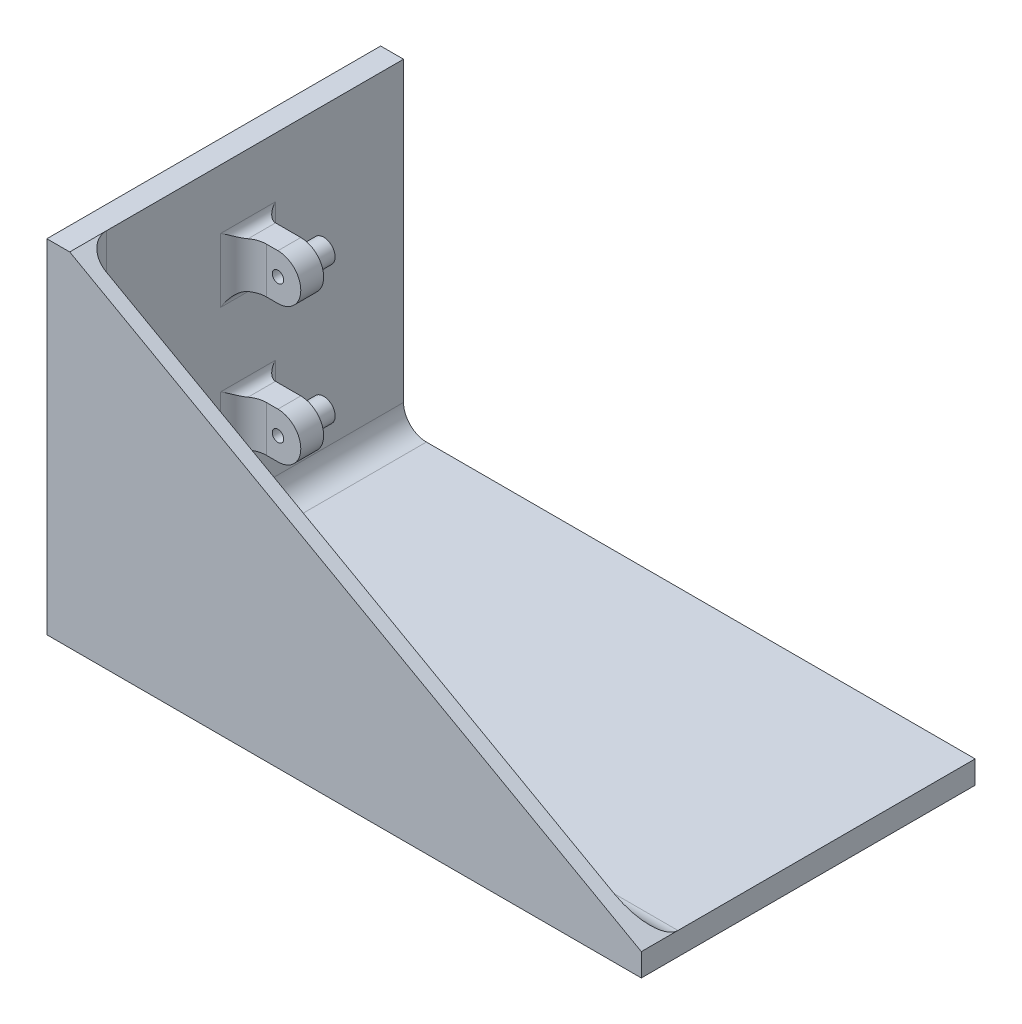
SolidWorks part; units mm, degrees
material "PET"
ref_plane "Piano frontale" through (0, 0, 0) normal (0, 0, 1) x (1, 0, 0)
ref_plane "Piano superiore" through (0, 0, 0) normal (0, 1, 0) x (1, 0, 0)
ref_plane "Piano destro" through (0, 0, 0) normal (1, 0, 0) x (0, 0, -1)
sketch "Schizzo1" plane through (0, 0, 0) normal (0, 0, 1) x (1, 0, 0)
  line L1 (0, 0) -> (-5, 0)
  line L2 (0, 0) -> (0, 70)
  line L3 (0, 70) -> (-5, 70)
  line L4 (-5, 0) -> (-5, 70)
  dimension "D1" = 70
  dimension "D2" = 5
extrude "Estrusione-Estrusione1" add sketch "Schizzo1" along normal blind 70
sketch "Schizzo2" plane through (0, 0, 70) normal (0, 0, 1) x (1, 0, 0)
  line L0 (0, 15) -> (0, 20)
  line L1 (0, 0) -> (0, 70) construction
  line L2 (0, 45) -> (0, 50)
  line L3 (7.5316, 55) -> (0, 55)
  line L4 (0, 55) -> (0, 45)
  line L5 (0, 45) -> (7.5316, 45)
  line L6 (7.5316, 25) -> (0, 25)
  line L7 (0, 25) -> (0, 15)
  line L8 (0, 15) -> (7.5316, 15)
  arc A0 (7.5316, 45) -> (7.5316, 55) centre (7.5316, 50) ccw
  arc A1 (7.5316, 15) -> (7.5316, 25) centre (7.5316, 20) ccw
  line M1 (0, 0) -> (0, 70)
  dimension "D1" = 10
  dimension "D2" = 10
extrude "Estrusione-Estrusione2" add sketch "Schizzo2" against normal blind 5 from offset 35 contours L5 A0 L3 M1 | L8 A1 L6 M1 region at (5.7836, 50, 70) region at (5.7836, 20, 70) offset against normal yes
sketch "Schizzo3" plane through (0, 0, 30) normal (0, 0, -1) x (-1, 0, 0)
  circle A0 centre (-7.5476, 50.0613) radius 2.5
  circle A1 centre (-7.5476, 19.9398) radius 2.5
  dimension "D1" = 5
  dimension "D2" = 5
extrude "Estrusione-Estrusione3" add sketch "Schizzo3" along normal blind 5
sketch "Schizzo4" plane through (0, 0, 0) normal (0, -1, 0) x (1, 0, 0)
  line L1 (-5, 0) -> (125, 0)
  line L2 (-5, 0) -> (-5, 70)
  line L3 (-5, 70) -> (125, 70)
  line L4 (125, 0) -> (125, 70)
extrude "Estrusione-Estrusione4" add sketch "Schizzo4" along normal blind 5
sketch "Schizzo5" plane through (0, 0, 25) normal (0, 0, -1) x (-1, 0, 0)
  circle A0 centre (-7.5476, 50.0613) radius 1.25
  circle A1 centre (-7.5476, 19.9398) radius 1.25
  dimension "D1" = 2.5
extrude "Taglio-Estrusione1" cut sketch "Schizzo5" against normal through all
sketch "Schizzo6" plane through (0, 0, 70) normal (0, 0, 1) x (1, 0, 0)
  line L0 (0, 70) -> (125, 0)
  line L7 (0, 0) -> (0, 70)
  line L8 (0, 70) -> (-5, 70)
  line L9 (-5, 70) -> (-5, -5)
  line L10 (-5, -5) -> (125, -5)
  line L11 (125, -5) -> (125, 0)
  line L12 (125, 0) -> (0, 0)
  line L13 (0, 0) -> (0, 70)
  line L14 (0, 70) -> (-5, 70)
  line L15 (-5, 70) -> (-5, -5)
  line L16 (-5, -5) -> (125, -5)
  line L17 (125, -5) -> (125, 0)
  line L18 (125, 0) -> (0, 0)
  line M7 (0, 0) -> (0, 70)
  line M8 (0, 70) -> (-5, 70)
  line M9 (-5, 70) -> (-5, -5)
  line M10 (-5, -5) -> (125, -5)
  line M11 (125, -5) -> (125, 0)
  line M12 (125, 0) -> (0, 0)
  dimension "D1" = 0
extrude "Estrusione-Estrusione5" add sketch "Schizzo6" along normal blind 3 contours M12 M7 M8 M9 M10 M11 | L0 M7 M12 region at (41.6667, 23.3333, 70) region at (-1.5008, 35, 70)
fillet "Raccordo1" radius 5 3 edges at (0, 0, 35) (0, 35, 70) (62.5, 0, 70)
fillet "Raccordo2" radius 5 2 edges at (0, 20, 35) (0, 50, 35)
fillet "Raccordo3" radius 2 2 edges at (0, 20, 30) (0, 50, 30)
fillet "Raccordo4" radius 2 4 edges at (0, 25, 34) (0, 15, 34) (0, 45, 34) (0, 55, 34)
ref_point "Punto1"
ref_point "Punto2"
ref_axis "Assi1" through (7.5476, 50.0613, 35) along (0, 0, -1)
ref_axis "Assi2" through (7.5316, 55, 30) along (-1, 0, 0)
